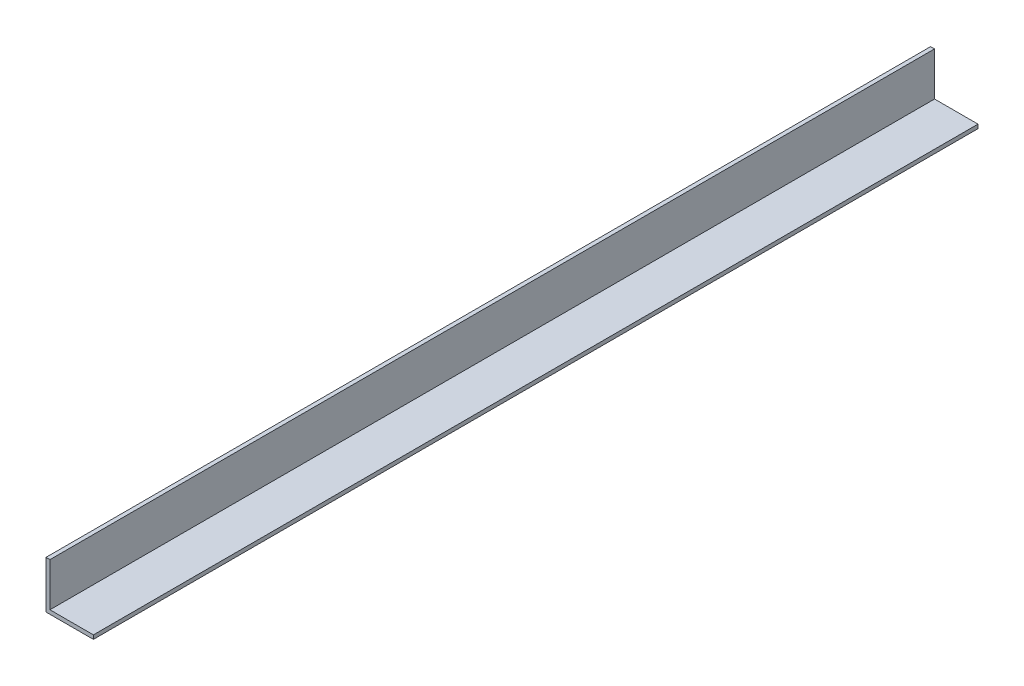
SolidWorks part; units mm, degrees
ref_plane "Front Plane" through (0, 0, 0) normal (0, 0, 1) x (1, 0, 0)
ref_plane "Top Plane" through (0, 0, 0) normal (0, 1, 0) x (1, 0, 0)
ref_plane "Right Plane" through (0, 0, 0) normal (1, 0, 0) x (0, 0, -1)
sketch "Sketch2" plane through (0, 0, 0) normal (0, 0, 1) x (1, 0, 0)
  line L0 (0, -9.525) -> (0, 9.525)
  line L1 (0, 9.525) -> (1.5875, 9.525)
  line L2 (1.5875, 9.525) -> (1.5875, -7.9375)
  line L3 (1.5875, -7.9375) -> (19.05, -7.9375)
  line L4 (19.05, -7.9375) -> (19.05, -9.525)
  line L5 (19.05, -9.525) -> (0, -9.525)
  point P4 (0, 0)
  dimension "D1" = 1.5875
  dimension "D2" = 1.5875
  dimension "D3" = 19.05
  dimension "D4" = 19.05
extrude "Boss-Extrude1" add sketch "Sketch2" along normal blind 355.6
